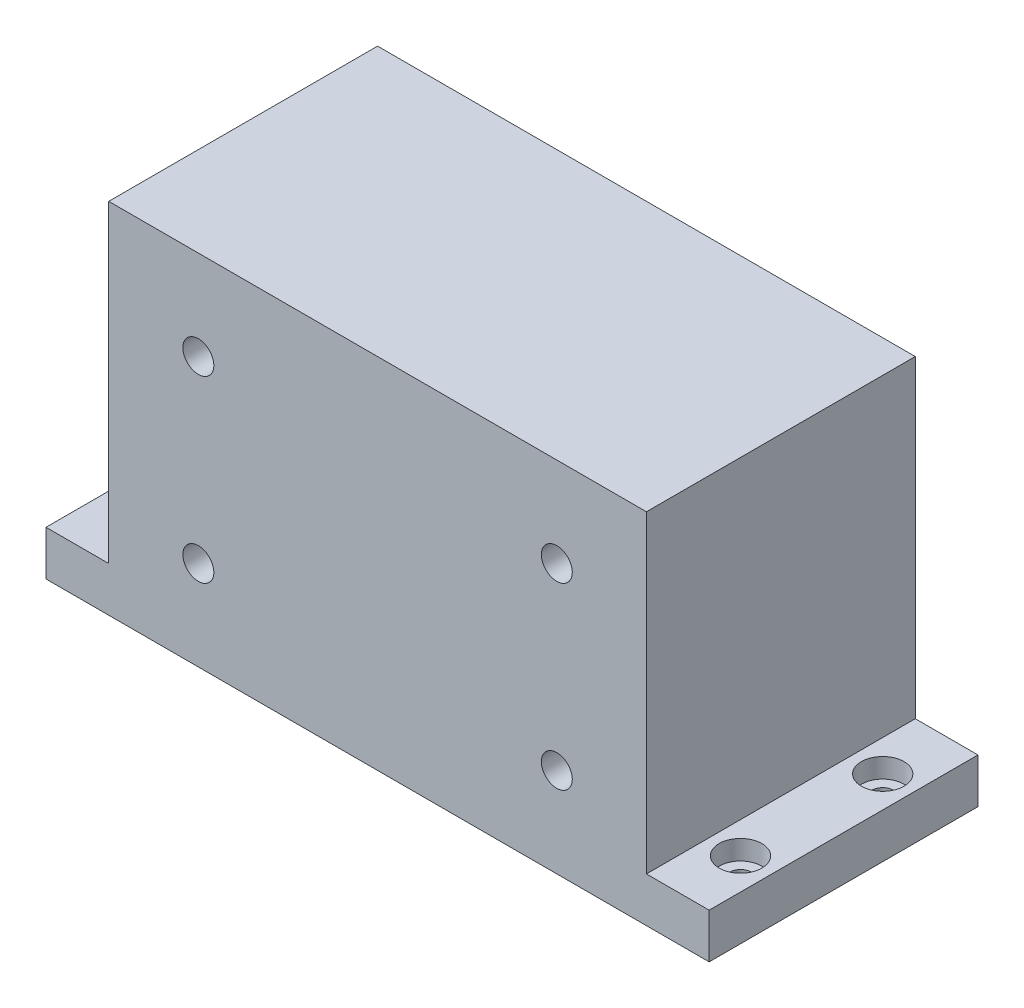
SolidWorks part; units mm, degrees
ref_plane "Front Plane" through (0, 0, 0) normal (0, 0, 1) x (1, 0, 0)
ref_plane "Top Plane" through (0, 0, 0) normal (0, 1, 0) x (1, 0, 0)
ref_plane "Right Plane" through (0, 0, 0) normal (1, 0, 0) x (0, 0, -1)
sketch "Sketch5" plane through (0, 0, 0) normal (0, 1, 0) x (1, 0, 0)
  line L1 (-30, 15) -> (30, 15)
  line L2 (-30, 15) -> (-30, -15)
  line L3 (-30, -15) -> (30, -15)
  line L4 (30, 15) -> (30, -15)
  line L5 (-30, 15) -> (30, -15) construction
  line L6 (-30, -15) -> (30, 15) construction
  point P0 (0, 0)
  dimension "D1" = 30
  dimension "D2" = 60
extrude "Boss-Extrude3" add sketch "Sketch5" along normal blind 40
sketch "Sketch6" plane through (0, 0, 15) normal (0, 0, 1) x (1, 0, 0)
  line L0 (0, 20) -> (-20, 20) construction
  line L3 (-25, 35) -> (25, 35)
  line L4 (-25, 35) -> (-25, 5)
  line L5 (-25, 5) -> (25, 5)
  line L6 (25, 35) -> (25, 5)
  line L7 (-25, 35) -> (25, 5) construction
  line L8 (-25, 5) -> (25, 35) construction
  line L10 (-20, 20) -> (-20, 30) construction
  line L12 (0, 20) -> (20, 20) construction
  line L13 (20, 20) -> (20, 10) construction
  line L14 (-20, 20) -> (-20, 10) construction
  line L15 (20, 20) -> (20, 30) construction
  line L16 (-30, 40) -> (-30, 0) construction
  line L17 (-30, 0) -> (30, 0) construction
  line L18 (-30, 40) -> (30, 40) construction
  point P8 (0, 20)
  dimension "D1" = 50
  dimension "D2" = 30
sketch "Sketch7" plane through (0, 0, -15) normal (0, 0, -1) x (-1, 0, 0)
  line L3 (-20, 10) -> (20, 10)
  line L4 (-20, 10) -> (-20, 30)
  line L5 (-20, 30) -> (20, 30)
  line L6 (20, 10) -> (20, 30)
  line L7 (-20, 10) -> (20, 30) construction
  line L8 (-20, 30) -> (20, 10) construction
  point P8 (0, 20)
  dimension "D1" = 20
  dimension "D2" = 40
extrude "Cut-Extrude1" cut sketch "Sketch7" against normal blind 15
fillet "Fillet1" radius 3 1 edges at (20, 10, -7.5)
fillet "Fillet2" radius 3 1 edges at (-20, 10, -7.5)
fillet "Fillet3" radius 3 1 edges at (-20, 30, -7.5)
fillet "Fillet4" radius 3 1 edges at (20, 30, -7.5)
sketch "Sketch8" plane through (0, 10, 0) normal (0, 1, 0) x (1, 0, 0)
  line L0 (0, 15) -> (0, 0) construction
  line L1 (17, 15) -> (-17, 15) construction
  dimension "D1" = 15
sketch "Sketch9" plane through (-30, 0, 0) normal (-1, 0, 0) x (0, 0, 1)
  line L0 (15, 40) -> (15, 0) construction
  line L1 (-15, 0) -> (15, 0)
  line L2 (-15, 0) -> (-15, 5)
  line L3 (-15, 5) -> (15, 5)
  line L4 (15, 0) -> (15, 5)
extrude "Boss-Extrude4" add sketch "Sketch9" along normal blind 7
sketch "Sketch10" plane through (30, 0, 0) normal (1, 0, 0) x (0, 0, -1)
  line L0 (15, 40) -> (15, 0) construction
  line L1 (-15, 0) -> (15, 0)
  line L2 (-15, 0) -> (-15, 5)
  line L3 (-15, 5) -> (15, 5)
  line L4 (15, 0) -> (15, 5)
extrude "Boss-Extrude5" add sketch "Sketch10" along normal blind 7
sketch "Sketch11" plane through (-30, 0, 0) normal (-1, 0, 0) x (0, 0, 1)
  line L0 (-15, 40) -> (0, 40) construction
  line L1 (-15, 40) -> (15, 40) construction
  line L2 (0, 40) -> (0, 5) construction
  line L3 (15, 5) -> (-15, 5) construction
  line L4 (0, 40) -> (-15, 5) construction
sketch "Sketch12" plane through (-30, 0, 0) normal (-1, 0, 0) x (0, 0, 1)
  circle A0 centre (-7.5315, 22.7105) radius 2
extrude "Cut-Extrude2" cut sketch "Sketch12" against normal blind 10
sketch "Sketch13" plane through (0, 0, 0) normal (0, -1, 0) x (-1, 0, 0)
  line L0 (-37, 15) -> (37, -15) construction
  line L1 (-37, -15) -> (37, 15) construction
  line L3 (-32, 10) -> (32, 10)
  line L4 (-32, 10) -> (-32, -10)
  line L5 (-32, -10) -> (32, -10)
  line L6 (32, 10) -> (32, -10)
  line L7 (-32, 10) -> (32, -10) construction
  line L8 (-32, -10) -> (32, 10) construction
  point P8 (0, 0)
  dimension "D1" = 64
  dimension "D2" = 20
extrude "Cut-Extrude3" cut sketch "Sketch13" against normal blind 1.5
sketch "Sketch14" plane through (0, 0, -15) normal (0, 0, -1) x (-1, 0, 0)
sketch "Sketch16" plane through (0, 5, 0) normal (0, 1, 0) x (1, 0, 0)
  line L3 (37, -15) -> (30, -15) construction
  line L6 (33.5, -15) -> (33.5, -8) construction
  line L7 (33.5004, 14.8485) -> (33.5184, 7.8485) construction
  point P11 (37, -15)
hole_wizard "CBORE for #2 Socket Head Cap Screw1" positions "3DSketch2" profile "Sketch17" counterbore size "#2" standard "ANSI Inch"
sketch3d "3DSketch2"
  point P0 (33.5, 5, 8)
  point P3 (33.5184, 5, -7.8485)
sketch "Sketch17" plane through (33.5, 5, 8) normal (1, 0, 0) x (0, 0, 1)
  line L0 (0, 0) -> (0, 15.7326)
  line L1 (0, 15.7326) -> (1.2192, 15)
  line L2 (1.2192, 15) -> (1.2192, 2.1844)
  line L3 (1.2192, 2.1844) -> (2.3812, 2.1844)
  line L4 (2.3812, 2.1844) -> (2.3812, 0)
  line L5 (2.3812, 0) -> (0, 0)
  line L10 (0, 15.7326) -> (-1.2192, 15) construction
  line L11 (0, -6.35) -> (0, 107.95) construction
  dimension "Hole Dia." = 2.4384
  dimension "Hole Depth" = 15
  dimension "C'Bore Dia." = 4.7625
  dimension "C'Bore Depth" = 2.1844
  dimension "Drill Angle" = 118
sketch "Sketch18" plane through (0, 5, 0) normal (0, 1, 0) x (1, 0, 0)
  line L2 (-33.5, -15) -> (-33.5, -8) construction
  line L3 (-37, -15) -> (-30, -15) construction
  line L4 (-33.5, 15) -> (-33.5, 8) construction
  line L5 (-37, 15) -> (-30, 15) construction
sketch "Sketch22" plane through (0, 0, -15) normal (0, 0, -1) x (-1, 0, 0)
  line L0 (25, 4) -> (25, 36) construction
  line L1 (-37, 0) -> (37, 0) construction
  line L3 (-30, 40) -> (-30, 0) construction
  line L4 (-25, 20) -> (-25, 36) construction
  line L7 (-25, 20) -> (-25, 4) construction
  line L8 (-25, 36) -> (25, 36) construction
  line L9 (25, 36) -> (25, 4) construction
hole_wizard "#2-56 Tapped Hole2" positions "3DSketch4" profile "Sketch23" tap size "#2-56" standard "ANSI Inch"
sketch3d "3DSketch4"
  point P0 (25, 36, -15)
  point P3 (25, 4, -15)
  point P6 (-25, 4, -15)
sketch "Sketch23" plane through (25, 36, -15) normal (1, 0, 0) x (0, 1, 0)
  line L0 (0, 0) -> (0, 15.5342)
  line L1 (0, 15.5342) -> (0.889, 15)
  line L2 (0.889, 15) -> (0.889, 0)
  line L5 (0.889, 0) -> (0, 0)
  line L10 (0, 15.5342) -> (-0.889, 15) construction
  line L11 (0, -6.35) -> (0, 107.95) construction
  dimension "Tap Drill Dia." = 1.778
  dimension "Tap Drill Depth" = 15
  dimension "Drill Angle" = 118
cosmetic thread "Hole Thread1" parameters "D1"=12, "D2"=2.1844
cosmetic thread "Hole Thread2" parameters "D1"=12, "D2"=2.1844
cosmetic thread "Hole Thread3" parameters "D1"=12, "D2"=2.1844
hole_wizard "#2-56 Tapped Hole3" positions "3DSketch5" profile "Sketch24" tap size "#2-56" standard "ANSI Inch"
sketch3d "3DSketch5"
  point P0 (-25, 36, -15)
sketch "Sketch24" plane through (-25, 36, -15) normal (1, 0, 0) x (0, 1, 0)
  line L0 (0, 0) -> (0, 15.5342)
  line L1 (0, 15.5342) -> (0.889, 15)
  line L2 (0.889, 15) -> (0.889, 0)
  line L5 (0.889, 0) -> (0, 0)
  line L10 (0, 15.5342) -> (-0.889, 15) construction
  line L11 (0, -6.35) -> (0, 107.95) construction
  dimension "Tap Drill Dia." = 1.778
  dimension "Tap Drill Depth" = 15
  dimension "Drill Angle" = 118
cosmetic thread "Hole Thread4" parameters "D1"=12, "D2"=2.1844
hole_wizard "CBORE for #2 Socket Head Cap Screw3" positions "Sketch25" profile "Sketch26" counterbore size "#2" standard "ANSI Inch"
sketch "Sketch25" plane through (0, 5, 0) normal (0, 1, 0) x (1, 0, 0)
  point P0 (-33.5, 8)
  point P3 (-33.5, -8)
sketch "Sketch26" plane through (-33.5, 5, -8) normal (1, 0, 0) x (0, 0, 1)
  line L0 (0, 0) -> (0, 15.7326)
  line L1 (0, 15.7326) -> (1.2192, 15)
  line L2 (1.2192, 15) -> (1.2192, 2.1844)
  line L3 (1.2192, 2.1844) -> (2.3812, 2.1844)
  line L4 (2.3812, 2.1844) -> (2.3812, 0)
  line L5 (2.3812, 0) -> (0, 0)
  line L10 (0, 15.7326) -> (-1.2192, 15) construction
  line L11 (0, -6.35) -> (0, 107.95) construction
  dimension "Hole Dia." = 2.4384
  dimension "Hole Depth" = 15
  dimension "C'Bore Dia." = 4.7625
  dimension "C'Bore Depth" = 2.1844
  dimension "Drill Angle" = 118
hole_wizard "#8-32 Tapped Hole1" positions "Sketch27" profile "Sketch28" tap size "#8-32" standard "ANSI Inch"
sketch "Sketch27" plane through (0, 0, 15) normal (0, 0, 1) x (1, 0, 0)
  point P0 (-20, 30)
  point P3 (-20, 10)
  point P6 (20, 10)
  point P9 (20, 30)
sketch "Sketch28" plane through (-20, 30, 15) normal (1, 0, 0) x (0, -1, 0)
  line L0 (0, 0) -> (0, 12.0378)
  line L1 (0, 12.0378) -> (1.7272, 11)
  line L2 (1.7272, 11) -> (1.7272, 0)
  line L5 (1.7272, 0) -> (0, 0)
  line L10 (0, 12.0378) -> (-1.7272, 11) construction
  line L11 (0, -6.35) -> (0, 107.95) construction
  dimension "Tap Drill Dia." = 3.4544
  dimension "Tap Drill Depth" = 11
  dimension "Drill Angle" = 118
cosmetic thread "Hole Thread5" parameters "D1"=8.33, "D2"=4.1656
cosmetic thread "Hole Thread6" parameters "D1"=8.33, "D2"=4.1656
cosmetic thread "Hole Thread7" parameters "D1"=8.33, "D2"=4.1656
cosmetic thread "Hole Thread8" parameters "D1"=8.33, "D2"=4.1656
sketch "Sketch29" plane through (0, 0, 0) normal (0, 0, -1) x (-1, 0, 0)
  line L0 (-20, 27) -> (-20, 13) construction
sketch "Sketch30" plane through (0, 0, 0) normal (0, 0, -1) x (-1, 0, 0)
  line L0 (20, 27) -> (20, 13) construction
  line L1 (-20, 27) -> (-20, 20) construction
  line L2 (-20, 27) -> (20, 13) construction
  line L3 (-20, 27) -> (-20, 13) construction
  line L4 (-20, 20) -> (0, 20) construction
  line L5 (0, 20) -> (20, 20) construction
  line L6 (-20, 20) -> (-10, 20) construction
  line L7 (20, 20) -> (10, 20) construction
  circle A0 centre (-10, 20) radius 1.5
  circle A1 centre (10, 20) radius 3
extrude "Cut-Extrude5" cut sketch "Sketch30" against normal blind 12 contours A0 | A1
